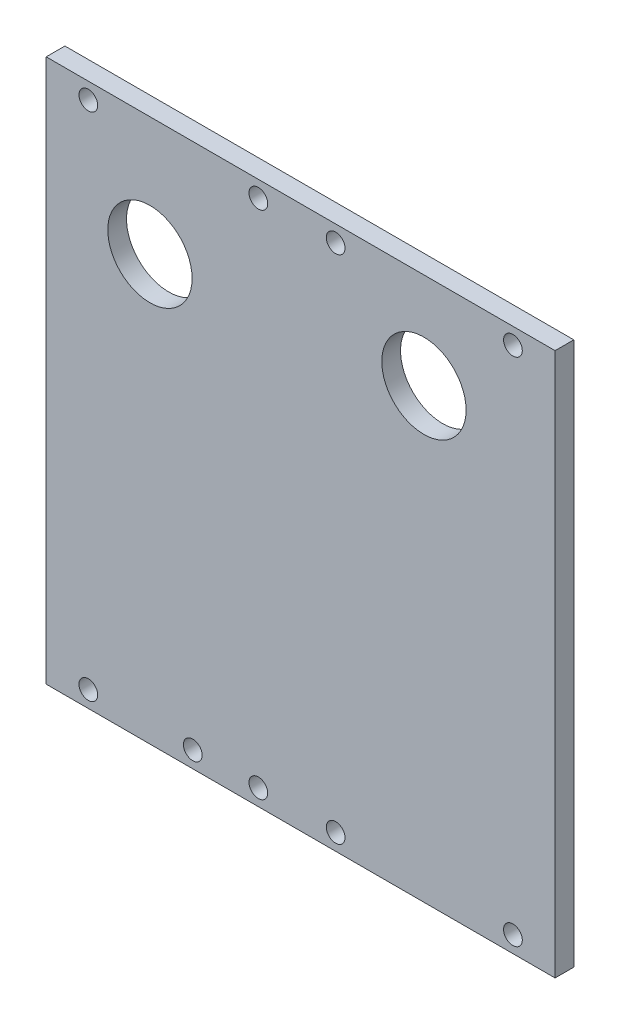
SolidWorks part; units mm, degrees
material "2024-T4"
ref_plane "Front Plane" through (0, 0, 0) normal (0, 0, 1) x (1, 0, 0)
ref_plane "Top Plane" through (0, 0, 0) normal (0, 1, 0) x (1, 0, 0)
ref_plane "Right Plane" through (0, 0, 0) normal (1, 0, 0) x (0, 0, -1)
sketch "Sketch1" plane through (0, 0, 0) normal (0, 0, 1) x (1, 0, 0)
  line L1 (-54.325, -58) -> (54.325, -58)
  line L2 (-54.325, -58) -> (-54.325, 58)
  line L3 (-54.325, 58) -> (54.325, 58)
  line L4 (54.325, -58) -> (54.325, 58)
  line L5 (-54.325, -58) -> (54.325, 58) construction
  line L6 (-54.325, 58) -> (54.325, -58) construction
  point P0 (0, 0)
  dimension "D1" = 108.65
  dimension "120" = 116
extrude "Boss-Extrude1" add sketch "Sketch1" along normal blind 4
sketch "Sketch2" plane through (0, 0, 4) normal (0, 0, 1) x (1, 0, 0)
  line L0 (54.325, 58) -> (-54.325, 58) construction
  line L1 (54.325, -58) -> (54.325, 58) construction
  circle A0 centre (26.325, 37.5) radius 9
  circle A1 centre (26.325, 37.5) radius 20 construction
  circle A3 centre (-32.175, 32.6) radius 9
  dimension "D1" = 18
  dimension "D3" = 40
  dimension "D4" = 28
  dimension "D5" = 25.4
  dimension "D2" = 20.5
  dimension "D6" = 58.5
extrude "Cut-Extrude1" cut sketch "Sketch2" against normal through all
sketch "Sketch3" plane through (54.325, 0, 0) normal (1, 0, 0) x (0, 0, -1)
  line L0 (-2, 58) -> (-2, 41.1774) construction
  line L1 (-4, 58) -> (0, 58) construction
  line L2 (0, 0) -> (7, 0) construction
  line L3 (7, 51) -> (0, 51) construction
  line L4 (0, -58) -> (0, 58) construction
  line L5 (-4, 54.5) -> (-16, 54.5)
  line L6 (0, 47.5) -> (12, 47.5)
  line L7 (0, 47.5) -> (0, 54.5)
  line L8 (0, 54.5) -> (12, 54.5)
  line L9 (12, 47.5) -> (12, 54.5)
  line L10 (-16, 47.5) -> (-16, 54.5)
  line L11 (-4, 47.5) -> (-16, 47.5)
  line L12 (-4, 47.5) -> (-4, 54.5)
  line L13 (0, -54.5) -> (12, -54.5)
  line L14 (12, -47.5) -> (12, -54.5)
  line L15 (0, -47.5) -> (12, -47.5)
  line L16 (0, -47.5) -> (0, -54.5)
  line L17 (-4, -47.5) -> (-4, -54.5)
  line L18 (-4, -47.5) -> (-16, -47.5)
  line L19 (-16, -47.5) -> (-16, -54.5)
  line L20 (-4, -54.5) -> (-16, -54.5)
  circle A0 centre (7, 51) radius 2
  circle A1 centre (-11, 51) radius 2
  circle A2 centre (7, -51) radius 2
  circle A3 centre (-11, -51) radius 2
  point P17 (0, 51)
  dimension "D2" = 4
  dimension "D1" = 7
  dimension "D3" = 7
  dimension "D4" = 7
  dimension "D5" = 12
extrude "Boss-Extrude2" [suppressed] add sketch "Sketch3" against normal blind 4
fillet "Fillet1" [suppressed] radius 4
fillet "Fillet2" [suppressed] radius 2
sketch "Sketch4" plane through (0, 0, 4) normal (0, 0, 1) x (1, 0, 0)
  line L0 (-54.325, -58) -> (54.325, -58) construction
  line L1 (-54.325, 58) -> (-50.325, 58) construction
  line L2 (-54.325, 58) -> (-54.325, -58) construction
  line L3 (-54.325, -58) -> (-50.325, -58) construction
  line L4 (-50.325, 58) -> (-50.325, -58) construction
  line L5 (-45.325, 51) -> (-50.325, 51) construction
  line L6 (-50.325, 54.5) -> (-40.325, 54.5) construction
  line L7 (-50.325, 54.5) -> (-50.325, 47.5) construction
  line L8 (-50.325, 47.5) -> (-40.325, 47.5) construction
  line L9 (-40.325, 54.5) -> (-40.325, 47.5) construction
  line L10 (-50.325, 0) -> (0, 0) construction
  line L11 (-14.025, 58) -> (-14.025, -58) construction
  line L12 (-18.025, 58) -> (-18.025, -58) construction
  line L13 (-18.025, -58) -> (-14.025, -58) construction
  line L14 (-18.025, 58) -> (-14.025, 58) construction
  line L15 (-14.025, 54.5) -> (-4.025, 54.5) construction
  line L16 (-14.025, 47.5) -> (-4.025, 47.5) construction
  line L17 (-4.025, 54.5) -> (-4.025, 47.5) construction
  line L18 (-9.025, 51) -> (-23.025, 51) construction
  line L19 (54.325, 58) -> (-54.325, 58) construction
  line L20 (-16.025, 58) -> (-16.025, 65.6289) construction
  line L21 (-9.025, 54.5) -> (7.475, 54.5) construction
  line L22 (54.325, -58) -> (54.325, 58) construction
  circle A0 centre (-45.325, 51) radius 2 construction
  circle A1 centre (-45.325, -51) radius 2 construction
  circle A2 centre (-9.025, 51) radius 2 construction
  circle A3 centre (-9.025, -51) radius 2 construction
  circle A4 centre (-23.025, 51) radius 2 construction
  circle A5 centre (-23.025, -51) radius 2 construction
  circle A6 centre (-45.325, 54.5) radius 2
  circle A7 centre (-45.325, -54.5) radius 2
  circle A8 centre (-23.025, 54.5) radius 2 construction
  circle A9 centre (-9.025, 54.5) radius 2
  circle A10 centre (-9.025, -54.5) radius 2
  circle A11 centre (-23.025, -54.5) radius 2
  circle A12 centre (7.475, 54.5) radius 2
  circle A13 centre (7.475, -54.5) radius 2
  circle A14 centre (45.325, 54.5) radius 2
  circle A15 centre (45.325, -54.5) radius 2
  point P15 (-50.325, 51)
  dimension "D1" = 4
  dimension "D2" = 4
  dimension "D3" = 7
  dimension "D4" = 10
  dimension "D5" = 5
  dimension "D6" = 7
  dimension "D8" = 36.3
  dimension "D9" = 5
  dimension "D10" = 3.5
  dimension "D11" = 3.5
  dimension "D12" = 16.5
  dimension "D13" = 9
  dimension "D7" = 2
extrude "Cut-Extrude2" cut sketch "Sketch4" against normal through all
equation "\"D11@Sketch4\"=\"D6@Sketch4\"/2"
